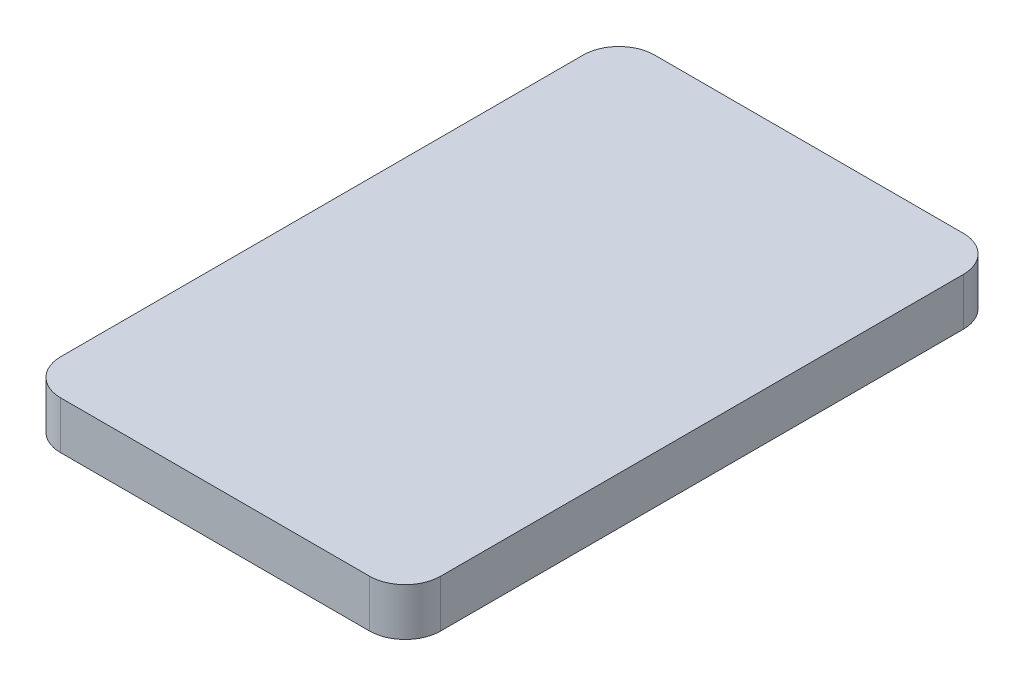
SolidWorks part; units mm, degrees
ref_plane "Front Plane" through (0, 0, 0) normal (0, 0, 1) x (1, 0, 0)
ref_plane "Top Plane" through (0, 0, 0) normal (0, 1, 0) x (1, 0, 0)
ref_plane "Right Plane" through (0, 0, 0) normal (1, 0, 0) x (0, 0, -1)
sketch "Sketch1" plane through (0, 0, 0) normal (0, 1, 0) x (1, 0, 0)
  line L1 (0, 0) -> (32, 0)
  line L2 (0, 0) -> (0, 50)
  line L3 (0, 50) -> (32, 50)
  line L4 (32, 0) -> (32, 50)
  dimension "D1" = 32
  dimension "D2" = 50
extrude "Boss-Extrude1" add sketch "Sketch1" along normal blind 4
fillet "Fillet1" radius 3 4 edges at (0, 2, -50) (32, 2, -50) (0, 2, 0) (32, 2, 0)
